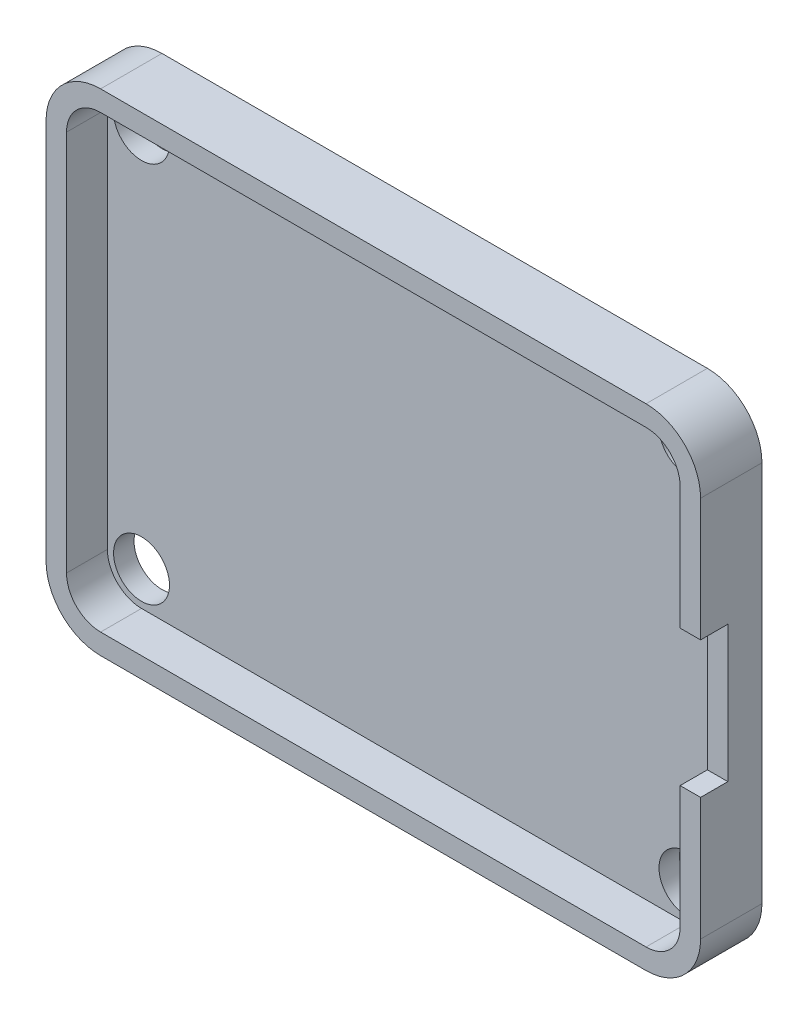
SolidWorks part; units mm, degrees
ref_plane "Front Plane" through (0, 0, 0) normal (0, 0, 1) x (1, 0, 0)
ref_plane "Top Plane" through (0, 0, 0) normal (0, 1, 0) x (1, 0, 0)
ref_plane "Right Plane" through (0, 0, 0) normal (1, 0, 0) x (0, 0, -1)
sketch "Sketch1" plane through (0, 0, 0) normal (0, 0, 1) x (1, 0, 0)
  line L1 (-20, -18) -> (20, -18)
  line L2 (-24, -14) -> (-24, 14)
  line L3 (-20, 18) -> (20, 18)
  line L4 (24, -14) -> (24, 14)
  line L5 (-24, -18) -> (24, 18) construction
  line L6 (-24, 18) -> (24, -18) construction
  arc A0 (-24, -14) -> (-20, -18) centre (-20, -14) ccw
  arc A1 (20, -18) -> (24, -14) centre (20, -14) ccw
  arc A2 (24, 14) -> (20, 18) centre (20, 14) ccw
  arc A3 (-20, 18) -> (-24, 14) centre (-20, 14) ccw
  circle A4 centre (-20, -14) radius 2.05
  circle A5 centre (-20, 14) radius 2.05
  circle A6 centre (20, 14) radius 2.05
  circle A7 centre (20, -14) radius 2.05
  point P0 (0, 0)
  dimension "D3" = 4
  dimension "D4" = 4
  dimension "D5" = 4
  dimension "D6" = 4
  dimension "D7" = 4.1
  dimension "D8" = 4.1
  dimension "D9" = 4.1
  dimension "D10" = 4.1
  dimension "D1" = 48
  dimension "D2" = 36
extrude "Boss-Extrude1" add sketch "Sketch1" along normal mid plane 4.5
sketch "Sketch3" plane through (0, 0, 2.25) normal (0, 0, 1) x (1, 0, 0)
  line L30 (22.5, -14) -> (22.5, 14)
  line L31 (20, 16.5) -> (-20, 16.5)
  line L32 (-22.5, 14) -> (-22.5, -14)
  line L33 (-20, -16.5) -> (20, -16.5)
  line L34 (22.5, -14) -> (22.5, 14)
  line L35 (20, 16.5) -> (-20, 16.5)
  line L36 (-22.5, 14) -> (-22.5, -14)
  line L37 (-20, -16.5) -> (20, -16.5)
  arc A24 (20, -16.5) -> (22.5, -14) centre (20, -14) ccw
  arc A25 (22.5, 14) -> (20, 16.5) centre (20, 14) ccw
  arc A26 (-20, 16.5) -> (-22.5, 14) centre (-20, 14) ccw
  arc A27 (-22.5, -14) -> (-20, -16.5) centre (-20, -14) ccw
  arc A28 (20, -16.5) -> (22.5, -14) centre (20, -14) ccw
  arc A29 (22.5, 14) -> (20, 16.5) centre (20, 14) ccw
  arc A30 (-20, 16.5) -> (-22.5, 14) centre (-20, 14) ccw
  arc A31 (-22.5, -14) -> (-20, -16.5) centre (-20, -14) ccw
  dimension "D1" = 1.5
extrude "Cut-Extrude2" cut sketch "Sketch3" against normal offset from surface (3 mm away) 1.5 up to face at (22.05, 14, -2.25)
sketch "Sketch4" plane through (0, 0, -2.25) normal (0, 0, -1) x (-1, 0, 0)
  line L0 (-24, 0) -> (24, 0) construction
  line L1 (-24, -14) -> (-24, 14) construction
  line L2 (24, 14) -> (24, -14) construction
  text T0 "HoekEncoder"
extrude "Cut-Extrude3" cut sketch "Sketch4" against normal blind 0.5
sketch "Sketch5" plane through (0, 0, 2.25) normal (0, 0, 1) x (1, 0, 0)
  line L0 (24, -14) -> (24, 14) construction
  line L1 (19, -5) -> (29, -5)
  line L2 (19, -5) -> (19, 5)
  line L3 (19, 5) -> (29, 5)
  line L4 (29, -5) -> (29, 5)
  line L5 (19, -5) -> (29, 5) construction
  line L6 (19, 5) -> (29, -5) construction
  point P0 (24, 0)
  dimension "D1" = 10
  dimension "D2" = 10
extrude "Cut-Extrude4" cut sketch "Sketch5" against normal blind 2
